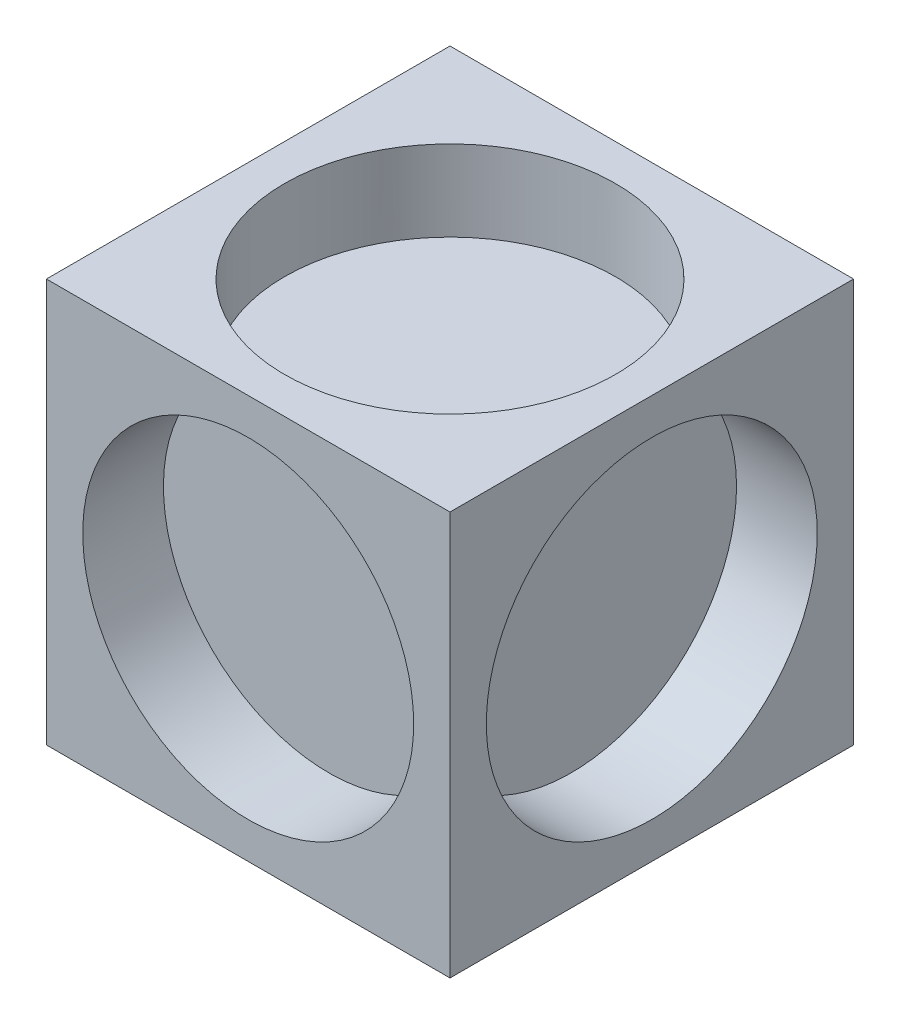
SolidWorks part; units mm, degrees
ref_plane "Front Plane" through (0, 0, 0) normal (0, 0, 1) x (1, 0, 0)
ref_plane "Top Plane" through (0, 0, 0) normal (0, 1, 0) x (1, 0, 0)
ref_plane "Right Plane" through (0, 0, 0) normal (1, 0, 0) x (0, 0, -1)
sketch "Sketch1" plane through (0, 0, 0) normal (0, 0, 1) x (1, 0, 0)
  line L1 (5, -5) -> (-5, -5)
  line L2 (5, -5) -> (5, 5)
  line L3 (5, 5) -> (-5, 5)
  line L4 (-5, -5) -> (-5, 5)
  line L5 (5, -5) -> (-5, 5) construction
  line L6 (5, 5) -> (-5, -5) construction
  point P0 (0, 0)
  dimension "D1" = 10
  dimension "D2" = 10
extrude "Boss-Extrude1" add sketch "Sketch1" along normal blind 5 and the other way blind 5
sketch "Sketch2" plane through (0, 5, 0) normal (0, 1, 0) x (1, 0, 0)
  circle A0 centre (0, 0) radius 4.1
  dimension "D1" = 8.2
extrude "Cut-Extrude1" cut sketch "Sketch2" against normal blind 2
sketch "Sketch5" plane through (0, 0, 5) normal (0, 0, 1) x (1, 0, 0)
  circle A0 centre (0, 0) radius 4.1
  dimension "D1" = 8.2
extrude "Cut-Extrude2" cut sketch "Sketch5" against normal blind 2
sketch "Sketch6" plane through (5, 0, 0) normal (1, 0, 0) x (0, 0, -1)
  circle A0 centre (0, 0) radius 4.1
  dimension "D1" = 8.2
extrude "Cut-Extrude3" cut sketch "Sketch6" against normal blind 2
